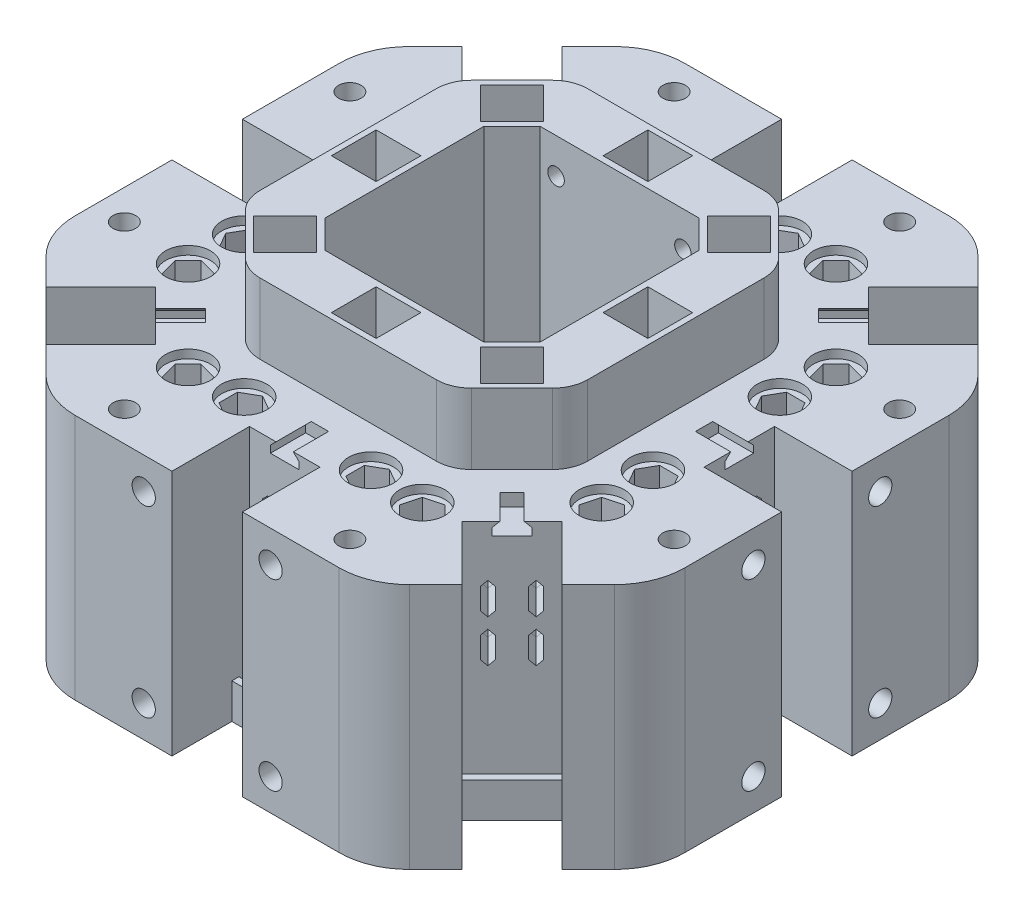
SolidWorks part; units mm, degrees
ref_plane "前视基准面" through (0, 0, 0) normal (0, 0, 1) x (1, 0, 0)
ref_plane "上视基准面" through (0, 0, 0) normal (0, 1, 0) x (1, 0, 0)
ref_plane "右视基准面" through (0, 0, 0) normal (1, 0, 0) x (0, 0, -1)
sketch "草图1" plane through (0, 0, 0) normal (0, 1, 0) x (1, 0, 0)
  line L0 (0, 0) -> (29, 0) construction
  line L1 (0, 0) -> (22.981, -22.981) construction
  line L2 (-29, 11.25) -> (-29, -11.25) construction
  line L3 (-30.9359, 15.026) -> (-15.026, 30.9359) construction
  line L4 (-22.981, 22.981) -> (0, 0) construction
  line L5 (-29, 0) -> (0, 0) construction
  line L6 (-40.25, 21.6218) -> (-40.25, -21.6218) construction
  line L7 (-40.25, 21.6218) -> (-21.6218, 40.25) construction
  line L8 (-22.981, 22.981) -> (-30.9359, 30.9359) construction
  line L9 (-29, 0) -> (-40.25, 0) construction
  line L10 (21.6218, 40.25) -> (40.25, 21.6218) construction
  line L11 (21.6218, 40.25) -> (-21.6218, 40.25) construction
  line L12 (40.25, -21.6218) -> (21.6218, -40.25) construction
  line L13 (40.25, -21.6218) -> (40.25, 21.6218) construction
  line L14 (-21.6218, -40.25) -> (-40.25, -21.6218) construction
  line L15 (-21.6218, -40.25) -> (21.6218, -40.25) construction
  line L16 (22.8645, 43.25) -> (-22.8645, 43.25)
  line L17 (-43.25, 22.8645) -> (-22.8645, 43.25)
  line L18 (-43.25, 22.8645) -> (-43.25, -22.8645)
  line L19 (-22.8645, -43.25) -> (-43.25, -22.8645)
  line L20 (-22.8645, -43.25) -> (22.8645, -43.25)
  line L21 (43.25, -22.8645) -> (22.8645, -43.25)
  line L22 (43.25, -22.8645) -> (43.25, 22.8645)
  line L23 (22.8645, 43.25) -> (43.25, 22.8645)
  line L24 (10.8523, 14.25) -> (-10.8523, 14.25)
  line L25 (-14.25, 10.8523) -> (-10.8523, 14.25)
  line L26 (-14.25, 10.8523) -> (-14.25, -10.8523)
  line L27 (-10.8523, -14.25) -> (-14.25, -10.8523)
  line L28 (-10.8523, -14.25) -> (10.8523, -14.25)
  line L29 (14.25, -10.8523) -> (10.8523, -14.25)
  line L30 (14.25, -10.8523) -> (14.25, 10.8523)
  line L31 (10.8523, 14.25) -> (14.25, 10.8523)
  circle A0 centre (0, 0) radius 14.25 construction
  circle A1 centre (29, 0) radius 11.25 construction
  circle A2 centre (22.981, -22.981) radius 11.25 construction
  circle A3 centre (0, -29) radius 11.25 construction
  circle A4 centre (-22.981, -22.981) radius 11.25 construction
  circle A5 centre (-29, 0) radius 11.25 construction
  circle A6 centre (-22.981, 22.981) radius 11.25 construction
  circle A7 centre (0, 29) radius 11.25 construction
  circle A8 centre (22.981, 22.981) radius 11.25 construction
  point P22 (0, 0)
  point P41 (0, 0)
  dimension "D1" = 28.5
  dimension "D2" = 22.5
  dimension "D3" = 29
  dimension "D4" = 32.5
  dimension "D5" = 45
  dimension "D8" = 3
  dimension "D9" = 26
  dimension "D6" = 4
  dimension "D7" = 4
sketch "草图3" plane through (0, 0, 0) normal (0, 1, 0) x (1, 0, 0)
  line L0 (43.25, -22.8645) -> (22.8645, -43.25) construction
  line L1 (-22.8645, -43.25) -> (22.8645, -43.25) construction
  line L2 (-22.8645, -43.25) -> (-43.25, -22.8645) construction
  line L3 (-43.25, 22.8645) -> (-43.25, -22.8645) construction
  line L4 (-43.25, 22.8645) -> (-22.8645, 43.25) construction
  line L5 (22.8645, 43.25) -> (-22.8645, 43.25) construction
  line L6 (22.8645, 43.25) -> (43.25, 22.8645) construction
  line L7 (43.25, -22.8645) -> (43.25, 22.8645) construction
  line L8 (43.25, -22.8645) -> (22.8645, -43.25)
  line L9 (-22.8645, -43.25) -> (22.8645, -43.25)
  line L10 (-22.8645, -43.25) -> (-43.25, -22.8645)
  line L11 (-43.25, 22.8645) -> (-43.25, -22.8645)
  line L12 (-43.25, 22.8645) -> (-22.8645, 43.25)
  line L13 (22.8645, 43.25) -> (-22.8645, 43.25)
  line L14 (22.8645, 43.25) -> (43.25, 22.8645)
  line L15 (43.25, -22.8645) -> (43.25, 22.8645)
extrude "凸台-拉伸1" add sketch "草图3" along normal blind 35
sketch "草图4" plane through (0, 35, 0) normal (0, 1, 0) x (1, 0, 0)
  line L0 (0, 0) -> (0, -29) construction
  line L1 (0, -29) -> (9, -29) construction
  line L2 (0, 0) -> (22.981, -22.981) construction
  line L3 (22.981, -22.981) -> (29.3449, -16.617) construction
  circle A0 centre (9, -29) radius 1.375
  circle A1 centre (-9, -29) radius 1.375
  circle A2 centre (29.3449, -16.617) radius 1.375
  circle A3 centre (16.617, -29.3449) radius 1.375
  circle A4 centre (-29.3449, -16.617) radius 1.375
  circle A5 centre (-16.617, -29.3449) radius 1.375
  circle A6 centre (-29, -9) radius 1.375
  circle A7 centre (-29, 9) radius 1.375
  circle A8 centre (-16.617, 29.3449) radius 1.375
  circle A9 centre (-29.3449, 16.617) radius 1.375
  circle A10 centre (-9, 29) radius 1.375
  circle A11 centre (9, 29) radius 1.375
  circle A12 centre (29.3449, 16.617) radius 1.375
  circle A13 centre (16.617, 29.3449) radius 1.375
  circle A14 centre (29, 9) radius 1.375
  circle A15 centre (29, -9) radius 1.375
  point P41 (0, 0)
  dimension "D2" = 2.75
  dimension "D1" = 18
  dimension "D3" = 18
  dimension "D4" = 4
extrude "切除-拉伸1" cut sketch "草图4" against normal through all
sketch "草图8" plane through (0, 35, 0) normal (0, 1, 0) x (1, 0, 0)
  line L0 (0, 0) -> (0, -29) construction
  line L1 (-6.735, -30.3077) -> (-9, -31.6154)
  line L2 (9, -26.3846) -> (6.735, -27.6923)
  line L3 (6.735, -27.6923) -> (6.735, -30.3077)
  line L4 (6.735, -30.3077) -> (9, -31.6154)
  line L5 (9, -31.6154) -> (11.265, -30.3077)
  line L6 (11.265, -30.3077) -> (11.265, -27.6923)
  line L7 (11.265, -27.6923) -> (9, -26.3846)
  line L8 (-6.735, -27.6923) -> (-6.735, -30.3077)
  line L9 (-9, -26.3846) -> (-6.735, -27.6923)
  line L10 (-11.265, -27.6923) -> (-9, -26.3846)
  line L11 (-11.265, -30.3077) -> (-11.265, -27.6923)
  line L12 (-9, -31.6154) -> (-11.265, -30.3077)
  line L13 (16.617, -29.3449) -> (14.7676, -27.4956) construction
  line L14 (14.7676, -27.4956) -> (14.0907, -30.0218)
  line L15 (14.0907, -30.0218) -> (15.9401, -31.8712)
  line L16 (15.9401, -31.8712) -> (18.4664, -31.1943)
  line L17 (18.4664, -31.1943) -> (19.1433, -28.668)
  line L18 (19.1433, -28.668) -> (17.2939, -26.8187)
  line L19 (17.2939, -26.8187) -> (14.7676, -27.4956)
  line L20 (9, -29) -> (9, -26.3846) construction
  line L22 (0, 0) -> (22.981, -22.981) construction
  line L23 (31.1943, -18.4664) -> (28.668, -19.1433)
  line L24 (31.8712, -15.9401) -> (31.1943, -18.4664)
  line L25 (30.0218, -14.0907) -> (31.8712, -15.9401)
  line L26 (27.4956, -14.7676) -> (30.0218, -14.0907)
  line L27 (26.8187, -17.2939) -> (27.4956, -14.7676)
  line L28 (28.668, -19.1433) -> (26.8187, -17.2939)
  line L29 (-27.6923, 6.735) -> (-30.3077, 6.735)
  line L30 (-30.3077, 6.735) -> (-31.6154, 9)
  line L31 (-31.6154, 9) -> (-30.3077, 11.265)
  line L32 (-30.3077, 11.265) -> (-27.6923, 11.265)
  line L33 (-27.6923, 11.265) -> (-26.3846, 9)
  line L34 (-26.3846, 9) -> (-27.6923, 6.735)
  line L35 (-30.3077, -11.265) -> (-27.6923, -11.265)
  line L36 (-27.6923, -11.265) -> (-26.3846, -9)
  line L37 (-26.3846, -9) -> (-27.6923, -6.735)
  line L38 (-27.6923, -6.735) -> (-30.3077, -6.735)
  line L39 (-30.3077, -6.735) -> (-31.6154, -9)
  line L40 (-31.6154, -9) -> (-30.3077, -11.265)
  line L41 (-31.1943, -18.4664) -> (-28.668, -19.1433)
  line L42 (-28.668, -19.1433) -> (-26.8187, -17.2939)
  line L43 (-26.8187, -17.2939) -> (-27.4956, -14.7676)
  line L44 (-27.4956, -14.7676) -> (-30.0218, -14.0907)
  line L45 (-30.0218, -14.0907) -> (-31.8712, -15.9401)
  line L46 (-31.8712, -15.9401) -> (-31.1943, -18.4664)
  line L47 (-18.4664, -31.1943) -> (-19.1433, -28.668)
  line L48 (-19.1433, -28.668) -> (-17.2939, -26.8187)
  line L49 (-17.2939, -26.8187) -> (-14.7676, -27.4956)
  line L50 (-14.7676, -27.4956) -> (-14.0907, -30.0218)
  line L51 (-14.0907, -30.0218) -> (-15.9401, -31.8712)
  line L52 (-15.9401, -31.8712) -> (-18.4664, -31.1943)
  line L53 (6.735, 27.6923) -> (6.735, 30.3077)
  line L54 (6.735, 30.3077) -> (9, 31.6154)
  line L55 (9, 31.6154) -> (11.265, 30.3077)
  line L56 (11.265, 30.3077) -> (11.265, 27.6923)
  line L57 (11.265, 27.6923) -> (9, 26.3846)
  line L58 (9, 26.3846) -> (6.735, 27.6923)
  line L59 (-11.265, 30.3077) -> (-11.265, 27.6923)
  line L60 (-11.265, 27.6923) -> (-9, 26.3846)
  line L61 (-9, 26.3846) -> (-6.735, 27.6923)
  line L62 (-6.735, 27.6923) -> (-6.735, 30.3077)
  line L63 (-6.735, 30.3077) -> (-9, 31.6154)
  line L64 (-9, 31.6154) -> (-11.265, 30.3077)
  line L65 (-18.4664, 31.1943) -> (-19.1433, 28.668)
  line L66 (-19.1433, 28.668) -> (-17.2939, 26.8187)
  line L67 (-17.2939, 26.8187) -> (-14.7676, 27.4956)
  line L68 (-14.7676, 27.4956) -> (-14.0907, 30.0218)
  line L69 (-14.0907, 30.0218) -> (-15.9401, 31.8712)
  line L70 (-15.9401, 31.8712) -> (-18.4664, 31.1943)
  line L71 (-31.1943, 18.4664) -> (-28.668, 19.1433)
  line L72 (-28.668, 19.1433) -> (-26.8187, 17.2939)
  line L73 (-26.8187, 17.2939) -> (-27.4956, 14.7676)
  line L74 (-27.4956, 14.7676) -> (-30.0218, 14.0907)
  line L75 (-30.0218, 14.0907) -> (-31.8712, 15.9401)
  line L76 (-31.8712, 15.9401) -> (-31.1943, 18.4664)
  line L77 (27.6923, -6.735) -> (30.3077, -6.735)
  line L78 (30.3077, -6.735) -> (31.6154, -9)
  line L79 (31.6154, -9) -> (30.3077, -11.265)
  line L80 (30.3077, -11.265) -> (27.6923, -11.265)
  line L81 (27.6923, -11.265) -> (26.3846, -9)
  line L82 (26.3846, -9) -> (27.6923, -6.735)
  line L83 (30.3077, 11.265) -> (27.6923, 11.265)
  line L84 (27.6923, 11.265) -> (26.3846, 9)
  line L85 (26.3846, 9) -> (27.6923, 6.735)
  line L86 (27.6923, 6.735) -> (30.3077, 6.735)
  line L87 (30.3077, 6.735) -> (31.6154, 9)
  line L88 (31.6154, 9) -> (30.3077, 11.265)
  line L89 (31.1943, 18.4664) -> (28.668, 19.1433)
  line L90 (28.668, 19.1433) -> (26.8187, 17.2939)
  line L91 (26.8187, 17.2939) -> (27.4956, 14.7676)
  line L92 (27.4956, 14.7676) -> (30.0218, 14.0907)
  line L93 (30.0218, 14.0907) -> (31.8712, 15.9401)
  line L94 (31.8712, 15.9401) -> (31.1943, 18.4664)
  line L95 (18.4664, 31.1943) -> (19.1433, 28.668)
  line L96 (19.1433, 28.668) -> (17.2939, 26.8187)
  line L97 (17.2939, 26.8187) -> (14.7676, 27.4956)
  line L98 (14.7676, 27.4956) -> (14.0907, 30.0218)
  line L99 (14.0907, 30.0218) -> (15.9401, 31.8712)
  line L100 (15.9401, 31.8712) -> (18.4664, 31.1943)
  circle A0 centre (9, -29) radius 2.265 construction
  circle A1 centre (16.617, -29.3449) radius 2.265 construction
  point P111 (0, 0)
  dimension "D1" = 4.53
  dimension "D2" = 4
extrude "切除-拉伸3" cut sketch "草图8" against normal blind 5
sketch "草图9" plane through (0, 35, 0) normal (0, 1, 0) x (1, 0, 0)
  line L0 (0, 0) -> (22.981, -22.981) construction
  circle A0 centre (9, -29) radius 3.19
  circle A1 centre (16.617, -29.3449) radius 3.19
  circle A2 centre (29, -9) radius 3.19
  circle A3 centre (29.3449, -16.617) radius 3.19
  circle A4 centre (-16.617, -29.3449) radius 3.19
  circle A5 centre (-9, -29) radius 3.19
  circle A6 centre (-29.3449, -16.617) radius 3.19
  circle A7 centre (-29, -9) radius 3.19
  circle A8 centre (-29.3449, 16.617) radius 3.19
  circle A9 centre (-29, 9) radius 3.19
  circle A10 centre (-16.617, 29.3449) radius 3.19
  circle A11 centre (-9, 29) radius 3.19
  circle A12 centre (16.617, 29.3449) radius 3.19
  circle A13 centre (9, 29) radius 3.19
  circle A14 centre (29.3449, 16.617) radius 3.19
  circle A15 centre (29, 9) radius 3.19
  point P41 (0, 0)
  dimension "D1" = 6.38
  dimension "D2" = 4
extrude "切除-拉伸4" cut sketch "草图9" against normal blind 1.2
sketch "草图5" plane through (0, 35, 0) normal (0, 1, 0) x (1, 0, 0)
  line L0 (0, 0) -> (0, -29) construction
  line L1 (-22.8645, -43.25) -> (22.8645, -43.25) construction
  line L2 (-5, -43.25) -> (5, -43.25)
  line L3 (-5, -43.25) -> (-5, -32.25)
  line L4 (-5, -32.25) -> (5, -32.25)
  line L5 (5, -43.25) -> (5, -32.25)
  line L6 (-5, -43.25) -> (5, -32.25) construction
  line L7 (-5, -32.25) -> (5, -43.25) construction
  line L8 (21.7435, -28.8146) -> (28.8146, -21.7435)
  line L9 (21.7435, -28.8146) -> (29.5217, -36.5928)
  line L10 (28.8146, -21.7435) -> (36.5928, -29.5217)
  line L11 (29.5217, -36.5928) -> (36.5928, -29.5217)
  line L12 (21.7435, -28.8146) -> (36.5928, -29.5217) construction
  line L13 (28.8146, -21.7435) -> (29.5217, -36.5928) construction
  line L14 (43.25, -22.8645) -> (22.8645, -43.25) construction
  line L15 (0, 0) -> (22.981, -22.981) construction
  line L16 (-36.5928, -29.5217) -> (-29.5217, -36.5928)
  line L17 (-21.7435, -28.8146) -> (-29.5217, -36.5928)
  line L18 (-28.8146, -21.7435) -> (-21.7435, -28.8146)
  line L19 (-28.8146, -21.7435) -> (-36.5928, -29.5217)
  line L20 (-43.25, -5) -> (-32.25, -5)
  line L21 (-32.25, 5) -> (-32.25, -5)
  line L22 (-43.25, 5) -> (-32.25, 5)
  line L23 (-43.25, 5) -> (-43.25, -5)
  line L24 (-29.5217, 36.5928) -> (-36.5928, 29.5217)
  line L25 (-28.8146, 21.7435) -> (-36.5928, 29.5217)
  line L26 (-21.7435, 28.8146) -> (-28.8146, 21.7435)
  line L27 (-21.7435, 28.8146) -> (-29.5217, 36.5928)
  line L28 (-5, 43.25) -> (-5, 32.25)
  line L29 (5, 32.25) -> (-5, 32.25)
  line L30 (5, 43.25) -> (5, 32.25)
  line L31 (5, 43.25) -> (-5, 43.25)
  line L32 (36.5928, 29.5217) -> (29.5217, 36.5928)
  line L33 (21.7435, 28.8146) -> (29.5217, 36.5928)
  line L34 (28.8146, 21.7435) -> (21.7435, 28.8146)
  line L35 (28.8146, 21.7435) -> (36.5928, 29.5217)
  line L36 (43.25, 5) -> (32.25, 5)
  line L37 (32.25, -5) -> (32.25, 5)
  line L38 (43.25, -5) -> (32.25, -5)
  line L39 (43.25, -5) -> (43.25, 5)
  point P4 (0, -37.75)
  point P12 (29.1682, -29.1682)
  point P47 (0, 0)
  dimension "D1" = 10
  dimension "D2" = 11
  dimension "D3" = 10
  dimension "D5" = 4
extrude "切除-拉伸2" cut sketch "草图5" against normal through all
sketch "草图10" plane through (0, 35, 0) normal (0, 1, 0) x (1, 0, 0)
  line L0 (14.25, -10.8523) -> (10.8523, -14.25) construction
  line L1 (-10.8523, -14.25) -> (10.8523, -14.25) construction
  line L2 (-10.8523, -14.25) -> (-14.25, -10.8523) construction
  line L3 (-14.25, 10.8523) -> (-14.25, -10.8523) construction
  line L4 (-14.25, 10.8523) -> (-10.8523, 14.25) construction
  line L5 (10.8523, 14.25) -> (-10.8523, 14.25) construction
  line L6 (10.8523, 14.25) -> (14.25, 10.8523) construction
  line L7 (14.25, -10.8523) -> (14.25, 10.8523) construction
  line L8 (14.25, -10.8523) -> (10.8523, -14.25) construction
  line L9 (-10.8523, -14.25) -> (10.8523, -14.25) construction
  line L10 (-10.8523, -14.25) -> (-14.25, -10.8523) construction
  line L11 (-14.25, 10.8523) -> (-14.25, -10.8523) construction
  line L12 (-14.25, 10.8523) -> (-10.8523, 14.25) construction
  line L13 (10.8523, 14.25) -> (-10.8523, 14.25) construction
  line L14 (10.8523, 14.25) -> (14.25, 10.8523) construction
  line L15 (14.25, -10.8523) -> (14.25, 10.8523) construction
  line L16 (23.25, -14.5802) -> (14.5802, -23.25)
  line L17 (-14.5802, -23.25) -> (14.5802, -23.25)
  line L18 (-14.5802, -23.25) -> (-23.25, -14.5802)
  line L19 (-23.25, 14.5802) -> (-23.25, -14.5802)
  line L20 (-23.25, 14.5802) -> (-14.5802, 23.25)
  line L21 (14.5802, 23.25) -> (-14.5802, 23.25)
  line L22 (14.5802, 23.25) -> (23.25, 14.5802)
  line L23 (23.25, -14.5802) -> (23.25, 14.5802)
  dimension "D2" = 5.75
  dimension "D1" = 9
extrude "凸台-拉伸2" add sketch "草图10" along normal blind 10
sketch "草图11" plane through (0, 45, 0) normal (0, 1, 0) x (1, 0, 0)
  line L0 (0, 0) -> (0, -19.275) construction
  line L1 (0, 0) -> (16.1044, -16.1044) construction
  line L2 (-3.175, -22.45) -> (3.175, -22.45)
  line L3 (-3.175, -22.45) -> (-3.175, -16.1)
  line L4 (-3.175, -16.1) -> (3.175, -16.1)
  line L5 (3.175, -22.45) -> (3.175, -16.1)
  line L6 (-3.175, -22.45) -> (3.175, -16.1) construction
  line L7 (-3.175, -16.1) -> (3.175, -22.45) construction
  line L8 (0, 0) -> (22.981, -22.981) construction
  line L9 (11.6142, -16.1044) -> (16.1044, -11.6142)
  line L10 (11.6142, -16.1044) -> (16.1044, -20.5945)
  line L11 (16.1044, -11.6142) -> (20.5945, -16.1044)
  line L12 (16.1044, -20.5945) -> (20.5945, -16.1044)
  line L13 (11.6142, -16.1044) -> (20.5945, -16.1044) construction
  line L14 (16.1044, -11.6142) -> (16.1044, -20.5945) construction
  line L15 (-14.5802, -23.25) -> (14.5802, -23.25) construction
  line L16 (14.5802, -23.25) -> (23.25, -14.5802) construction
  line L17 (-22.45, -3.175) -> (-16.1, -3.175)
  line L18 (-16.1, 3.175) -> (-16.1, -3.175)
  line L19 (-22.45, 3.175) -> (-16.1, 3.175)
  line L20 (-22.45, 3.175) -> (-22.45, -3.175)
  line L21 (-11.6142, -16.1044) -> (-16.1044, -20.5945)
  line L22 (-20.5945, -16.1044) -> (-16.1044, -20.5945)
  line L23 (-16.1044, -11.6142) -> (-20.5945, -16.1044)
  line L24 (-16.1044, -11.6142) -> (-11.6142, -16.1044)
  line L25 (-3.175, 22.45) -> (-3.175, 16.1)
  line L26 (3.175, 16.1) -> (-3.175, 16.1)
  line L27 (3.175, 22.45) -> (3.175, 16.1)
  line L28 (3.175, 22.45) -> (-3.175, 22.45)
  line L29 (-16.1044, 11.6142) -> (-20.5945, 16.1044)
  line L30 (-16.1044, 20.5945) -> (-20.5945, 16.1044)
  line L31 (-11.6142, 16.1044) -> (-16.1044, 20.5945)
  line L32 (-11.6142, 16.1044) -> (-16.1044, 11.6142)
  line L33 (22.45, 3.175) -> (16.1, 3.175)
  line L34 (16.1, -3.175) -> (16.1, 3.175)
  line L35 (22.45, -3.175) -> (16.1, -3.175)
  line L36 (22.45, -3.175) -> (22.45, 3.175)
  line L37 (11.6142, 16.1044) -> (16.1044, 20.5945)
  line L38 (20.5945, 16.1044) -> (16.1044, 20.5945)
  line L39 (16.1044, 11.6142) -> (20.5945, 16.1044)
  line L40 (16.1044, 11.6142) -> (11.6142, 16.1044)
  point P45 (0, 0)
  dimension "D1" = 6.35
  dimension "D2" = 0.8
  dimension "D3" = 0.8
  dimension "D4" = 4
extrude "切除-拉伸5" cut sketch "草图11" against normal blind 6.5
ref_plane "基准面1" through (0, 17.5, 0) normal (0, 1, 0) x (1, 0, 0)
mirror "镜向1" about plane through (0, 17.5, 0) normal (0, 1, 0) of "切除-拉伸4", "切除-拉伸3"
sketch "草图12" plane through (0, 0, 0) normal (0, -1, 0) x (1, 0, 0)
  line L0 (11.6142, -16.1044) -> (16.1044, -11.6142) construction
  line L1 (16.1044, -11.6142) -> (20.5945, -16.1044) construction
  line L2 (20.5945, -16.1044) -> (16.1044, -20.5945) construction
  line L3 (16.1044, -20.5945) -> (11.6142, -16.1044) construction
  line L4 (16.1, -3.175) -> (16.1, 3.175) construction
  line L5 (16.1, 3.175) -> (22.45, 3.175) construction
  line L6 (22.45, 3.175) -> (22.45, -3.175) construction
  line L7 (22.45, -3.175) -> (16.1, -3.175) construction
  line L8 (11.6142, 16.1044) -> (16.1044, 20.5945) construction
  line L9 (16.1044, 20.5945) -> (20.5945, 16.1044) construction
  line L10 (20.5945, 16.1044) -> (16.1044, 11.6142) construction
  line L11 (16.1044, 11.6142) -> (11.6142, 16.1044) construction
  line L12 (3.175, 22.45) -> (3.175, 16.1) construction
  line L13 (3.175, 16.1) -> (-3.175, 16.1) construction
  line L14 (-3.175, 16.1) -> (-3.175, 22.45) construction
  line L15 (-3.175, 22.45) -> (3.175, 22.45) construction
  line L16 (-11.6142, 16.1044) -> (-16.1044, 11.6142) construction
  line L17 (-16.1044, 11.6142) -> (-20.5945, 16.1044) construction
  line L18 (-20.5945, 16.1044) -> (-16.1044, 20.5945) construction
  line L19 (-16.1044, 20.5945) -> (-11.6142, 16.1044) construction
  line L20 (-16.1, 3.175) -> (-16.1, -3.175) construction
  line L21 (-16.1, -3.175) -> (-22.45, -3.175) construction
  line L22 (-22.45, -3.175) -> (-22.45, 3.175) construction
  line L23 (-22.45, 3.175) -> (-16.1, 3.175) construction
  line L24 (-16.1044, -11.6142) -> (-11.6142, -16.1044) construction
  line L25 (-11.6142, -16.1044) -> (-16.1044, -20.5945) construction
  line L26 (-16.1044, -20.5945) -> (-20.5945, -16.1044) construction
  line L27 (-20.5945, -16.1044) -> (-16.1044, -11.6142) construction
  line L28 (-3.175, -16.1) -> (3.175, -16.1) construction
  line L29 (3.175, -16.1) -> (3.175, -22.45) construction
  line L30 (3.175, -22.45) -> (-3.175, -22.45) construction
  line L31 (-3.175, -22.45) -> (-3.175, -16.1) construction
  line L32 (11.6142, -16.1044) -> (16.1044, -11.6142)
  line L33 (16.1044, -11.6142) -> (20.5945, -16.1044)
  line L34 (20.5945, -16.1044) -> (16.1044, -20.5945)
  line L35 (16.1044, -20.5945) -> (11.6142, -16.1044)
  line L36 (16.1, -3.175) -> (16.1, 3.175)
  line L37 (16.1, 3.175) -> (22.45, 3.175)
  line L38 (22.45, 3.175) -> (22.45, -3.175)
  line L39 (22.45, -3.175) -> (16.1, -3.175)
  line L40 (11.6142, 16.1044) -> (16.1044, 20.5945)
  line L41 (16.1044, 20.5945) -> (20.5945, 16.1044)
  line L42 (20.5945, 16.1044) -> (16.1044, 11.6142)
  line L43 (16.1044, 11.6142) -> (11.6142, 16.1044)
  line L44 (3.175, 22.45) -> (3.175, 16.1)
  line L45 (3.175, 16.1) -> (-3.175, 16.1)
  line L46 (-3.175, 16.1) -> (-3.175, 22.45)
  line L47 (-3.175, 22.45) -> (3.175, 22.45)
  line L48 (-11.6142, 16.1044) -> (-16.1044, 11.6142)
  line L49 (-16.1044, 11.6142) -> (-20.5945, 16.1044)
  line L50 (-20.5945, 16.1044) -> (-16.1044, 20.5945)
  line L51 (-16.1044, 20.5945) -> (-11.6142, 16.1044)
  line L52 (-16.1, 3.175) -> (-16.1, -3.175)
  line L53 (-16.1, -3.175) -> (-22.45, -3.175)
  line L54 (-22.45, -3.175) -> (-22.45, 3.175)
  line L55 (-22.45, 3.175) -> (-16.1, 3.175)
  line L56 (-16.1044, -11.6142) -> (-11.6142, -16.1044)
  line L57 (-11.6142, -16.1044) -> (-16.1044, -20.5945)
  line L58 (-16.1044, -20.5945) -> (-20.5945, -16.1044)
  line L59 (-20.5945, -16.1044) -> (-16.1044, -11.6142)
  line L60 (-3.175, -16.1) -> (3.175, -16.1)
  line L61 (3.175, -16.1) -> (3.175, -22.45)
  line L62 (3.175, -22.45) -> (-3.175, -22.45)
  line L63 (-3.175, -22.45) -> (-3.175, -16.1)
extrude "切除-拉伸6" cut sketch "草图12" against normal blind 6.5
sketch "草图13" plane through (0, 35, 0) normal (0, 1, 0) x (1, 0, 0)
  line L0 (5, -32.25) -> (-5, -32.25) construction
  line L1 (-2.025, -30.75) -> (2.025, -30.75)
  line L2 (-2.025, -30.75) -> (-2.025, -27.25)
  line L3 (-2.025, -27.25) -> (2.025, -27.25)
  line L4 (2.025, -30.75) -> (2.025, -27.25)
  line L5 (-2.025, -30.75) -> (2.025, -27.25) construction
  line L6 (-2.025, -27.25) -> (2.025, -30.75) construction
  line L7 (-2.025, -30.75) -> (2.025, -30.75)
  line L8 (-2.025, -30.75) -> (-2.025, -32.25)
  line L9 (-2.025, -32.25) -> (2.025, -32.25)
  line L10 (2.025, -30.75) -> (2.025, -32.25)
  line L11 (0, 0) -> (25.2791, -25.2791) construction
  line L12 (28.8146, -21.7435) -> (21.7435, -28.8146) construction
  line L13 (22.7865, -25.6503) -> (20.3116, -23.1754)
  line L14 (22.7865, -25.6503) -> (25.6503, -22.7865)
  line L15 (20.3116, -23.1754) -> (23.1754, -20.3116)
  line L16 (25.6503, -22.7865) -> (23.1754, -20.3116)
  line L17 (22.7865, -25.6503) -> (23.1754, -20.3116) construction
  line L18 (20.3116, -23.1754) -> (25.6503, -22.7865) construction
  line L19 (25.6503, -22.7865) -> (22.7865, -25.6503)
  line L20 (25.6503, -22.7865) -> (26.711, -23.8472)
  line L21 (22.7865, -25.6503) -> (23.8472, -26.711)
  line L22 (26.711, -23.8472) -> (23.8472, -26.711)
  line L23 (16.617, -29.3449) -> (29.3449, -16.617) construction
  line L24 (-9, -29) -> (9, -29) construction
  point P0 (0, -29)
  point P16 (22.981, -22.981)
  dimension "D1" = 4.05
  dimension "D2" = 3.5
extrude "切除-拉伸7" cut sketch "草图13" against normal blind 1.8 contours L10 L1 L8 L9 | L1 L4 L3 L2 | L22 L20 L14 L21 | L14 L16 L15 L13 region at (0, 35, 29) region at (0, 35, 31.5) region at (22.981, 35, 22.981) region at (24.7487, 35, 24.7487)
sketch "草图22" plane through (0, 0, 32.25) normal (0, 0, 1) x (1, 0, 0)
  line L0 (2.025, 35) -> (2.025, 34.2)
  line L2 (2.025, 34.2) -> (1.225, 35)
  line L3 (-2.025, 35) -> (2.025, 35) construction
  line L4 (1.225, 35) -> (2.025, 35)
  line L5 (0, 33.2) -> (0, 36.1981) construction
  line L6 (-2.025, 33.2) -> (2.025, 33.2) construction
  line L7 (-1.225, 35) -> (-2.025, 35)
  line L8 (-2.025, 34.2) -> (-1.225, 35)
  line L9 (-2.025, 35) -> (-2.025, 34.2)
  dimension "D1" = 0.8
  dimension "D2" = 45
extrude "凸台-拉伸3" add sketch "草图22" against normal blind 5
sketch "草图23" plane through (25.2791, 0, 25.2791) normal (0.7071, 0, 0.7071) x (0.7071, 0, -0.7071)
  line L0 (2.025, 35) -> (2.025, 34.2)
  line L1 (2.025, 33.2) -> (2.025, 35) construction
  line L2 (2.025, 34.2) -> (1.225, 35)
  line L3 (-6.1305, 35) -> (6.1305, 35) construction
  line L4 (1.225, 35) -> (2.025, 35)
  line L5 (0, 33.2) -> (0, 35.8295) construction
  line L6 (2.025, 33.2) -> (-2.025, 33.2) construction
  line L7 (-1.225, 35) -> (-2.025, 35)
  line L8 (-2.025, 34.2) -> (-1.225, 35)
  line L9 (-2.025, 35) -> (-2.025, 34.2)
  dimension "D1" = 45
  dimension "D2" = 0.8
extrude "凸台-拉伸4" add sketch "草图23" against normal blind 5
ref_axis "基准轴1" through (0, 47.25, 0) along (0, -1, 0)
sketch "草图14" plane through (0, 0, 0) normal (0, -1, 0) x (1, 0, 0)
  line L0 (0, 0) -> (22.981, 22.981) construction
  line L1 (25.6503, 22.7865) -> (23.1754, 20.3116)
  line L2 (25.6503, 22.7865) -> (22.7865, 25.6503)
  line L3 (23.1754, 20.3116) -> (20.3116, 23.1754)
  line L4 (22.7865, 25.6503) -> (20.3116, 23.1754)
  line L5 (25.6503, 22.7865) -> (20.3116, 23.1754) construction
  line L6 (23.1754, 20.3116) -> (22.7865, 25.6503) construction
  line L7 (22.7865, 25.6503) -> (25.6503, 22.7865)
  line L8 (22.7865, 25.6503) -> (23.8472, 26.711)
  line L9 (25.6503, 22.7865) -> (26.711, 23.8472)
  line L10 (23.8472, 26.711) -> (26.711, 23.8472)
  line L11 (28.8146, 21.7435) -> (21.7435, 28.8146) construction
  dimension "D1" = 3.5
  dimension "D2" = 4.05
extrude "切除-拉伸8" [suppressed] cut sketch "草图14" against normal blind 1.8 contours L10 L8 L2 L9 | L2 L4 L3 L1
pattern_circular "阵列(圆周)1" count 4 every 90 about axis through (0, 47.25, 0) along (0, -1, 0) of "切除-拉伸7", "凸台-拉伸3", "凸台-拉伸4"
sketch "草图15" plane through (0, 38.5, 0) normal (0, 1, 0) x (1, 0, 0)
  line L0 (0, 0) -> (0, -22.45) construction
  line L1 (-3.175, -22.45) -> (3.175, -22.45) construction
  line L2 (3.175, -19.275) -> (0, -19.275) construction
  line L3 (3.175, -22.45) -> (3.175, -16.1) construction
  line L4 (1.675, -20.775) -> (1.675, -17.775)
  line L5 (1.675, -17.775) -> (2.425, -17.025)
  line L6 (2.425, -17.025) -> (3.175, -17.775)
  line L7 (3.175, -17.775) -> (3.175, -20.775)
  line L8 (2.425, -21.525) -> (3.175, -20.775)
  line L9 (1.675, -20.775) -> (2.425, -21.525)
  line L10 (-2.425, -17.025) -> (-3.175, -17.775)
  line L11 (-1.675, -17.775) -> (-2.425, -17.025)
  line L12 (-1.675, -20.775) -> (-1.675, -17.775)
  line L13 (-1.675, -20.775) -> (-2.425, -21.525)
  line L14 (-2.425, -21.525) -> (-3.175, -20.775)
  line L15 (-3.175, -17.775) -> (-3.175, -20.775)
  point P20 (1.675, -19.275)
  dimension "D1" = 90
  dimension "D2" = 1.5
  dimension "D3" = 3
sketch "草图16" plane through (0, 0, 0) normal (1, 0, 0) x (0, 0, -1)
  line L0 (-19.275, 38.5) -> (-19.275, 33.5)
  line L1 (-27.275, 25.5) -> (-32.25, 25.5)
  line L3 (-32.25, 0) -> (-32.25, 35) construction
  line L4 (-32.25, 0) -> (-32.25, 35) construction
  arc A0 (-19.275, 33.5) -> (-27.275, 25.5) centre (-27.275, 33.5) cw
  dimension "D1" = 8
  dimension "D2" = 13
sweep "切除-扫描1" cut profiles "草图15" path "草图16"
sketch "草图17" plane through (0, 38.5, 0) normal (0, 1, 0) x (1, 0, 0)
  line L0 (0, 0) -> (18.3494, -18.3494) construction
  line L1 (16.1044, -20.5945) -> (20.5945, -16.1044) construction
  line L2 (18.3494, -13.8593) -> (16.1044, -16.1044) construction
  line L3 (20.5945, -16.1044) -> (16.1044, -11.6142) construction
  line L4 (18.3494, -15.9806) -> (16.2281, -13.8593)
  line L5 (16.2281, -13.8593) -> (16.2281, -12.7986)
  line L6 (16.2281, -12.7986) -> (17.2888, -12.7986)
  line L7 (20.5945, -16.1044) -> (16.1044, -11.6142) construction
  line L8 (17.2888, -12.7986) -> (19.4101, -14.92)
  line L9 (19.4101, -15.9806) -> (19.4101, -14.92)
  line L10 (18.3494, -15.9806) -> (19.4101, -15.9806)
  line L11 (15.9806, -18.3494) -> (15.9806, -19.4101)
  line L12 (15.9806, -19.4101) -> (14.92, -19.4101)
  line L13 (12.7986, -17.2888) -> (14.92, -19.4101)
  line L14 (12.7986, -16.2281) -> (12.7986, -17.2888)
  line L15 (13.8593, -16.2281) -> (12.7986, -16.2281)
  line L16 (15.9806, -18.3494) -> (13.8593, -16.2281)
  point P21 (17.2888, -14.92)
  dimension "D1" = 3
  dimension "D2" = 1.5
ref_plane "基准面2" through (0, 0, 0) normal (-0.7071, 0, 0.7071) x (0.7071, 0, 0.7071)
sketch "草图18" plane through (0, 0, 0) normal (-0.7071, 0, 0.7071) x (0.7071, 0, 0.7071)
  line L0 (22.775, 38.5) -> (22.775, 33.5)
  line L1 (30.775, 25.5) -> (35.75, 25.5)
  line L2 (35.75, 0) -> (35.75, 35) construction
  line L3 (35.75, 0) -> (35.75, 35) construction
  arc A0 (22.775, 33.5) -> (30.775, 25.5) centre (30.775, 33.5) ccw
  dimension "D1" = 8
  dimension "D2" = 13
sweep "切除-扫描2" cut profiles "草图17" path "草图18"
pattern_circular "阵列(圆周)2" count 4 every 90 about axis through (0, 47.25, 0) along (0, -1, 0) of "切除-扫描2", "切除-扫描1"
ref_plane "基准面3" through (0, 22.5, 0) normal (0, 1, 0) x (1, 0, 0)
mirror "镜向2" about plane through (0, 22.5, 0) normal (0, 1, 0) of "阵列(圆周)2"
sketch "草图20" plane through (0, 45, 0) normal (0, 1, 0) x (1, 0, 0)
  line L0 (14.25, -10.8523) -> (10.8523, -14.25) construction
  line L1 (-10.8523, -14.25) -> (10.8523, -14.25) construction
  line L2 (-10.8523, -14.25) -> (-14.25, -10.8523) construction
  line L3 (-14.25, 10.8523) -> (-14.25, -10.8523) construction
  line L4 (-14.25, 10.8523) -> (-10.8523, 14.25) construction
  line L5 (10.8523, 14.25) -> (-10.8523, 14.25) construction
  line L6 (10.8523, 14.25) -> (14.25, 10.8523) construction
  line L7 (14.25, -10.8523) -> (14.25, 10.8523) construction
  line L8 (14.25, -10.8523) -> (10.8523, -14.25) construction
  line L9 (-10.8523, -14.25) -> (10.8523, -14.25) construction
  line L10 (-10.8523, -14.25) -> (-14.25, -10.8523) construction
  line L11 (-14.25, 10.8523) -> (-14.25, -10.8523) construction
  line L12 (-14.25, 10.8523) -> (-10.8523, 14.25) construction
  line L13 (10.8523, 14.25) -> (-10.8523, 14.25) construction
  line L14 (10.8523, 14.25) -> (14.25, 10.8523) construction
  line L15 (14.25, -10.8523) -> (14.25, 10.8523) construction
  line L16 (-15.25, 11.2665) -> (-11.2665, 15.25)
  line L17 (11.2665, 15.25) -> (-11.2665, 15.25)
  line L18 (11.2665, 15.25) -> (15.25, 11.2665)
  line L19 (15.25, -11.2665) -> (15.25, 11.2665)
  line L20 (15.25, -11.2665) -> (11.2665, -15.25)
  line L21 (-11.2665, -15.25) -> (11.2665, -15.25)
  line L22 (-11.2665, -15.25) -> (-15.25, -11.2665)
  line L23 (-15.25, 11.2665) -> (-15.25, -11.2665)
  dimension "D1" = 1
extrude "切除-拉伸9" cut sketch "草图20" against normal through all
sketch "草图21" plane through (0, 45, 0) normal (0, 1, 0) x (1, 0, 0)
  line L0 (0, 0) -> (-12.5313, -23.25)
  line L1 (-14.5802, -23.25) -> (14.5802, -23.25) construction
  line L2 (-12.5313, -23.25) -> (-12.5313, -43.25)
  line L3 (-22.8645, -43.25) -> (22.8645, -43.25) construction
  line L4 (-12.5313, -43.25) -> (22.8645, -43.25)
  line L5 (22.8645, -43.25) -> (43.25, -22.8645)
  line L6 (43.25, -22.8645) -> (43.25, -14.7099)
  line L7 (43.25, -22.8645) -> (43.25, 22.8645) construction
  line L8 (23.25, -11.7342) -> (43.25, -14.7099)
  line L9 (23.25, -14.5802) -> (23.25, 14.5802) construction
  line L10 (0, 0) -> (23.25, -11.7342)
  circle A0 centre (22.981, -22.981) radius 11.25 construction
extrude "切除-拉伸10" [suppressed] cut sketch "草图21" against normal through all flip side to cut
sketch "草图24" plane through (0, 0, 0) normal (0, -1, 0) x (1, 0, 0)
  line L0 (0, 0) -> (11.25, 11.25) construction
  line L1 (0, 0) -> (9.5117, 0) construction
  line L2 (15.25, 11.2665) -> (15.25, -11.2665) construction
  line L3 (7.25, 7.25) -> (15.25, 7.25)
  line L4 (7.25, 7.25) -> (7.25, 15.25)
  line L5 (7.25, 15.25) -> (11.2665, 15.25)
  line L6 (15.25, 7.25) -> (15.25, 11.2665)
  line L7 (7.25, 7.25) -> (15.25, 15.25) construction
  line L8 (7.25, 15.25) -> (15.25, 7.25) construction
  line L9 (11.2665, 15.25) -> (15.25, 11.2665) construction
  line L10 (11.2665, 15.25) -> (15.25, 11.2665)
  line L11 (7.25, -7.25) -> (7.25, -15.25)
  line L12 (7.25, -15.25) -> (11.2665, -15.25)
  line L13 (15.25, -11.2665) -> (11.2665, -15.25)
  line L14 (15.25, -7.25) -> (15.25, -11.2665)
  line L15 (7.25, -7.25) -> (15.25, -7.25)
  line L16 (-7.25, -7.25) -> (-15.25, -7.25)
  line L17 (-15.25, -7.25) -> (-15.25, -11.2665)
  line L18 (-11.2665, -15.25) -> (-15.25, -11.2665)
  line L19 (-7.25, -15.25) -> (-11.2665, -15.25)
  line L20 (-7.25, -7.25) -> (-7.25, -15.25)
  line L21 (-7.25, 7.25) -> (-7.25, 15.25)
  line L22 (-7.25, 15.25) -> (-11.2665, 15.25)
  line L23 (-15.25, 11.2665) -> (-11.2665, 15.25)
  line L24 (-15.25, 7.25) -> (-15.25, 11.2665)
  line L25 (-7.25, 7.25) -> (-15.25, 7.25)
  point P30 (0, 0)
  dimension "D1" = 45
  dimension "D2" = 8
  dimension "D3" = 4
extrude "凸台-拉伸5" add sketch "草图24" against normal blind 4
chamfer "倒角1" distance 2.5 angle 45 4 edges at (-7.25, 2, -7.25) (-7.25, 2, 7.25) (7.25, 2, -7.25) (7.25, 2, 7.25)
sketch "草图25" plane through (0, 0, 0) normal (0, -1, 0) x (1, 0, 0)
  line L0 (0, 0) -> (8.5, -8.5) construction
  line L1 (9.75, -7.25) -> (7.25, -9.75) construction
  circle A0 centre (11, -11) radius 1.175
  circle A1 centre (-11, -11) radius 1.175
  circle A2 centre (-11, 11) radius 1.175
  circle A3 centre (11, 11) radius 1.175
  point P16 (0, 0)
  dimension "D1" = 2.35
  dimension "D2" = 11
  dimension "D3" = 4
extrude "切除-拉伸11" cut sketch "草图25" against normal through all
sketch "草图27" plane through (0, 0, 0) normal (0, -1, 0) x (1, 0, 0)
  circle A0 centre (11, -11) radius 2.05
  circle A1 centre (-11, -11) radius 2.05
  circle A2 centre (-11, 11) radius 2.05
  circle A3 centre (11, 11) radius 2.05
  point P12 (0, 0)
  dimension "D1" = 4.1
  dimension "D2" = 4
extrude "切除-拉伸12" [suppressed] cut sketch "草图27" against normal blind 1.5
sketch "草图28" plane through (0, 0, 0) normal (0, -1, 0) x (1, 0, 0)
  line L0 (0, 0) -> (33.9498, -33.9498) construction
  line L1 (0, 0) -> (0, -40.7169) construction
  circle A0 centre (16, -39) radius 1.6
  circle A1 centre (39, -16) radius 1.6
  circle A2 centre (-39, -16) radius 1.6
  circle A3 centre (-16, -39) radius 1.6
  circle A4 centre (-16, 39) radius 1.6
  circle A5 centre (-39, 16) radius 1.6
  circle A6 centre (39, 16) radius 1.6
  circle A7 centre (16, 39) radius 1.6
  point P23 (0, 0)
  dimension "D2" = 3.2
  dimension "D1" = 45
  dimension "D3" = 32
  dimension "D4" = 39
  dimension "D5" = 4
extrude "切除-拉伸13" cut sketch "草图28" against normal blind 6
mirror "镜向3" about plane through (0, 17.5, 0) normal (0, 1, 0) of "切除-拉伸13"
sketch "草图30" plane through (0, 0, -23.25) normal (0, 0, -1) x (-1, 0, 0)
  line L0 (0, 0) -> (0, 51.512) construction
  line L1 (-14.5802, 45) -> (14.5802, 45) construction
  circle A0 centre (9, 40) radius 1.175
  circle A1 centre (-9, 40) radius 1.175
  dimension "D1" = 2.35
  dimension "D2" = 18
  dimension "D3" = 5
extrude "切除-拉伸14" cut sketch "草图30" against normal blind 20
sketch "草图31" plane through (0, 0, -23.25) normal (0, 0, -1) x (-1, 0, 0)
  circle A0 centre (9, 40) radius 2.1
  circle A1 centre (-9, 40) radius 2.1
  dimension "D1" = 4.2
extrude "切除-拉伸15" cut sketch "草图31" against normal blind 1.5
fillet "圆角1" radius 10 8 edges at (-22.8645, 17.5, -43.25) (-43.25, 17.5, -22.8645) (-43.25, 17.5, 22.8645) (-22.8645, 17.5, 43.25) (22.8645, 17.5, 43.25) (43.25, 17.5, 22.8645) (43.25, 17.5, -22.8645) (22.8645, 17.5, -43.25)
fillet "圆角2" radius 5 8 edges at (23.25, 40, 14.5802) (14.5802, 40, 23.25) (-23.25, 40, 14.5802) (-23.25, 40, -14.5802) (-14.5802, 40, -23.25) (14.5802, 40, -23.25) (23.25, 40, -14.5802) (-14.5802, 40, 23.25)
sketch "草图33" plane through (-43.25, 0, 0) normal (-1, 0, 0) x (0, 0, 1)
  line L0 (5, 17.5) -> (33.69, 17.5) construction
  line L1 (5, 0) -> (5, 35) construction
  line L2 (0, 0) -> (0, 48.4154) construction
  line L3 (5, 0) -> (-5, 0) construction
  line L4 (5, 35) -> (18.7223, 35) construction
  circle A0 centre (9, 30.5) radius 1.65
  circle A1 centre (9, 4.5) radius 1.65
  circle A2 centre (-9, 4.5) radius 1.65
  circle A3 centre (-9, 30.5) radius 1.65
  dimension "D1" = 3.3
  dimension "D2" = 9
  dimension "D3" = 4.5
extrude "切除-拉伸16" cut sketch "草图33" against normal blind 5
pattern_circular "阵列(圆周)3" count 4 every 90 about axis through (0, 47.25, 0) along (0, -1, 0) of "切除-拉伸16"
fillet "圆角3" [suppressed] radius 3
sketch "草图34" plane through (0, 0, 0) normal (0, -1, 0) x (1, 0, 0)
  line L0 (-5, 32.25) -> (-5, 43.25) construction
  line L1 (-5, 33.75) -> (5, 33.75)
  line L2 (-5, 33.75) -> (-5, 34.75)
  line L3 (-5, 34.75) -> (5, 34.75)
  line L4 (5, 33.75) -> (5, 34.75)
  line L5 (5, 43.25) -> (5, 32.25) construction
  line L6 (5, 32.25) -> (-5, 32.25) construction
  line L7 (22.8042, 29.8753) -> (29.8753, 22.8042)
  line L8 (22.8042, 29.8753) -> (23.5113, 30.5824)
  line L9 (29.8753, 22.8042) -> (30.5824, 23.5113)
  line L10 (23.5113, 30.5824) -> (30.5824, 23.5113)
  line L11 (21.7435, 28.8146) -> (29.5217, 36.5928) construction
  line L12 (36.5928, 29.5217) -> (28.8146, 21.7435) construction
  line L13 (28.8146, 21.7435) -> (21.7435, 28.8146) construction
  dimension "D1" = 1
  dimension "D2" = 1.5
  dimension "D3" = 1.5
extrude "凸台-拉伸6" add sketch "草图34" against normal blind 5
equation "\"D3@草图34\"=\"D2@草图34\""
